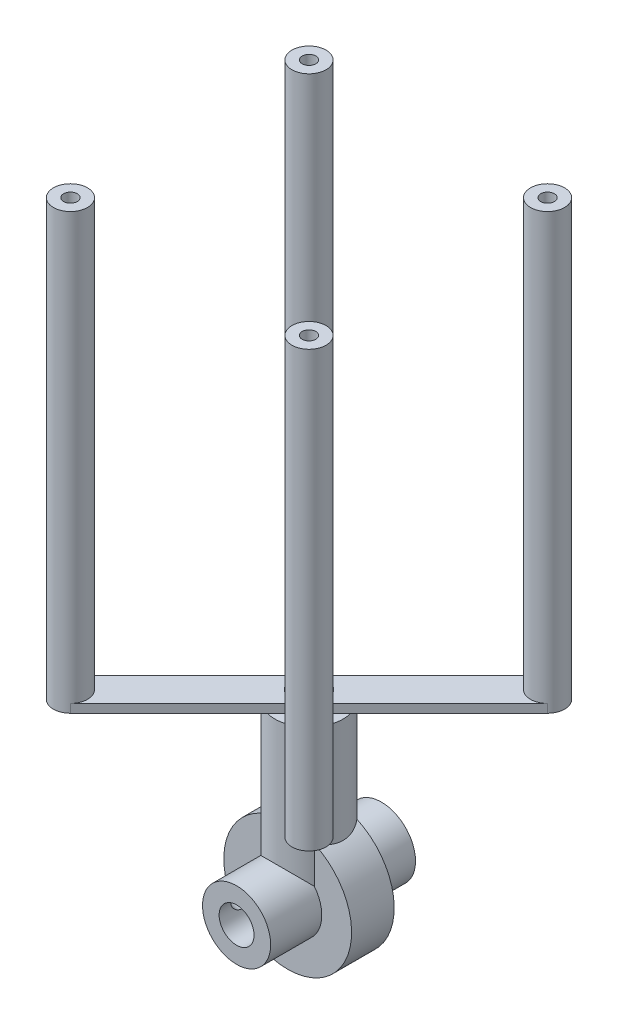
SolidWorks part; units mm, degrees
ref_plane "Front Plane" through (0, 0, 0) normal (0, 0, 1) x (1, 0, 0)
ref_plane "Top Plane" through (0, 0, 0) normal (0, 1, 0) x (1, 0, 0)
ref_plane "Right Plane" through (0, 0, 0) normal (1, 0, 0) x (0, 0, -1)
sketch "Sketch1" plane through (0, 0, 0) normal (0, 0, 1) x (1, 0, 0)
  circle A0 centre (102.3412, 36.4161) radius 7.5
  circle A1 centre (102.3412, 36.4161) radius 2.05
extrude "Boss-Extrude1" add sketch "Sketch1" along normal blind 2.5
sketch "Sketch2" plane through (0, 0, 2.5) normal (0, 0, 1) x (1, 0, 0)
  circle A0 centre (102.3412, 36.4161) radius 2.05
  circle A1 centre (102.3412, 36.4161) radius 4
extrude "Boss-Extrude2" add sketch "Sketch2" along normal blind 6
sketch "Sketch7" plane through (0, 0, 0) normal (0, 0, -1) x (-1, 0, 0)
  line L1 (-106.3412, 36.4161) -> (-102.3412, 36.4161)
  line L2 (-106.3412, 36.4161) -> (-106.3412, 55.1033)
  line L3 (-106.3412, 55.1033) -> (-102.3412, 55.1033)
  line L4 (-102.3412, 36.4161) -> (-102.3412, 55.1033)
revolve "Revolve7" add sketch "Sketch7" angle 180 about L4 reverse direction yes
sketch "Sketch8" plane through (0, 0, 0) normal (0, 0, -1) x (-1, 0, 0)
  line L0 (-104.3912, 36.4161) -> (-100.2912, 36.4161) construction
  line L1 (-102.3412, 36.4161) -> (-104.3912, 36.4161)
  line L2 (-102.3412, 36.4161) -> (-102.3412, 55.1033)
  line L3 (-102.3412, 55.1033) -> (-104.3912, 55.1033)
  line L4 (-104.3912, 36.4161) -> (-104.3912, 55.1033)
  line L5 (-98.3412, 55.1033) -> (-106.3412, 55.1033) construction
revolve "Cut-Revolve2" cut sketch "Sketch8" angle 360 about L2
sketch "Sketch9" plane through (0, 0, 0) normal (0, 0, -1) x (-1, 0, 0)
  circle A0 centre (-102.3412, 36.4161) radius 2.05
extrude "Cut-Extrude1" cut sketch "Sketch9" against normal blind 5
mirror "Mirror1" about plane through (102.3412, 36.4161, 0) normal (0, 0, 1) of "Cut-Extrude1", "Revolve7", "Boss-Extrude2", "Boss-Extrude1", "Cut-Revolve2"
sketch "Sketch10" plane through (0, 55.1033, 0) normal (0, 1, 0) x (1, 0, 0)
  line L0 (102.3412, 0) -> (88.3412, 14) construction
  line L1 (121.3412, -19) -> (83.3412, -19) construction
  line L2 (121.3412, -19) -> (121.3412, 19) construction
  line L3 (121.3412, 19) -> (83.3412, 19) construction
  line L4 (83.3412, -19) -> (83.3412, 19) construction
  line L5 (121.3412, -19) -> (83.3412, 19) construction
  line L6 (121.3412, 19) -> (83.3412, -19) construction
  line L11 (102.3412, 0) -> (116.3412, 14) construction
  line L14 (102.3412, 0) -> (116.3412, -14) construction
  line L17 (102.3412, 0) -> (88.3412, -14) construction
  line L20 (102.3412, 2.8284) -> (89.7554, 15.4142)
  line L21 (105.1696, 0) -> (117.7554, -12.5858)
  line L22 (105.1696, 0) -> (117.7554, 12.5858)
  line L23 (102.3412, -2.8284) -> (89.7554, -15.4142)
  line L24 (102.3412, -2.8284) -> (114.927, -15.4142)
  line L25 (99.5128, 0) -> (86.927, 12.5858)
  line L26 (99.5128, 0) -> (86.927, -12.5858)
  line L27 (102.3412, 2.8284) -> (114.927, 15.4142)
  arc A4 (89.7554, 15.4142) -> (86.927, 12.5858) centre (88.3412, 14) ccw
  arc A6 (117.7554, 12.5858) -> (114.927, 15.4142) centre (116.3412, 14) ccw
  arc A8 (114.927, -15.4142) -> (117.7554, -12.5858) centre (116.3412, -14) ccw
  arc A10 (86.927, -12.5858) -> (89.7554, -15.4142) centre (88.3412, -14) ccw
  circle A11 centre (102.3412, 0) radius 2.05
  point P0 (102.3412, 0)
  point P8 (95.3412, 7)
  point P18 (109.3412, 7)
  point P25 (109.3412, -7)
  point P32 (95.3412, -7)
  point P38 (102.3412, 0)
  dimension "D1" = 38
  dimension "D2" = 38
  dimension "D3" = 5
  dimension "D4" = 5
extrude "Boss-Extrude3" add sketch "Sketch10" along normal blind 1
sketch "Sketch11" plane through (0, 56.1033, 0) normal (0, 1, 0) x (1, 0, 0)
  circle A4 centre (88.3412, 14) radius 2
  circle A5 centre (116.3412, 14) radius 2
  circle A6 centre (116.3412, -14) radius 2
  circle A7 centre (88.3412, -14) radius 2
  point P2 (0, 0)
  point P11 (102.3412, 0)
  dimension "D1" = 4
extrude "Boss-Extrude4" add sketch "Sketch11" along normal blind 50
hole_wizard "M3x0.5 Tapped Hole1" positions "3DSketch1" profile "Sketch12" tap size "M3x0.5" standard "ANSI Metric" end condition up to next
sketch3d "3DSketch1"
  point P0 (98.588, 37.7993, 5.9237)
  point P2 (98.537, 37.6524, -5.5187)
cosmetic thread "Hole Thread1" parameters "D2"=3
cosmetic thread "Hole Thread2" parameters "D2"=3
sketch "Sketch12" plane through (98.588, 37.7993, 5.9237) normal (0, 0, 1) x (-0.3458, -0.9383, 0)
  line L0 (0, 0) -> (0, 1.95)
  line L1 (0, 1.95) -> (1.25, 1.95)
  line L2 (1.25, 1.95) -> (1.25, 0)
  line L5 (1.25, 0) -> (0, 0)
  line L11 (0, -6.35) -> (0, 107.95) construction
  dimension "Thru Tap Drill Dia." = 2.5
  dimension "Thru Tap Drill Depth" = 1.95
sketch "Sketch14" plane through (0, 106.1033, 0) normal (0, 1, 0) x (1, 0, 0)
  circle A0 centre (88.3412, 14) radius 1 construction
  circle A1 centre (116.3412, 14) radius 1 construction
  circle A2 centre (116.3412, -14) radius 1 construction
  circle A3 centre (88.3412, -14) radius 1 construction
  point P12 (102.3412, 0)
  dimension "D1" = 4
hole_wizard "M2x0.4 Tapped Hole1" positions "3DSketch2" profile "Sketch15" tap size "M2x0.4" standard "ANSI Metric"
sketch3d "3DSketch2"
  point P0 (88.3412, 106.1033, -14)
  point P3 (88.3412, 106.1033, 14)
  point P6 (116.3412, 106.1033, 14)
  point P9 (116.3412, 106.1033, -14)
cosmetic thread "Hole Thread3" parameters "D2"=2
cosmetic thread "Hole Thread4" parameters "D2"=2
cosmetic thread "Hole Thread5" parameters "D2"=2
cosmetic thread "Hole Thread6" parameters "D2"=2
sketch "Sketch15" plane through (88.3412, 106.1033, -14) normal (1, 0, 0) x (0, 0, 1)
  line L0 (0, 0) -> (0, 18.4807)
  line L1 (0, 18.4807) -> (0.8, 18)
  line L2 (0.8, 18) -> (0.8, 0)
  line L5 (0.8, 0) -> (0, 0)
  line L10 (0, 18.4807) -> (-0.8, 18) construction
  line L11 (0, -6.35) -> (0, 107.95) construction
  dimension "Tap Drill Dia." = 1.6
  dimension "Tap Drill Depth" = 18
  dimension "Drill Angle" = 118
